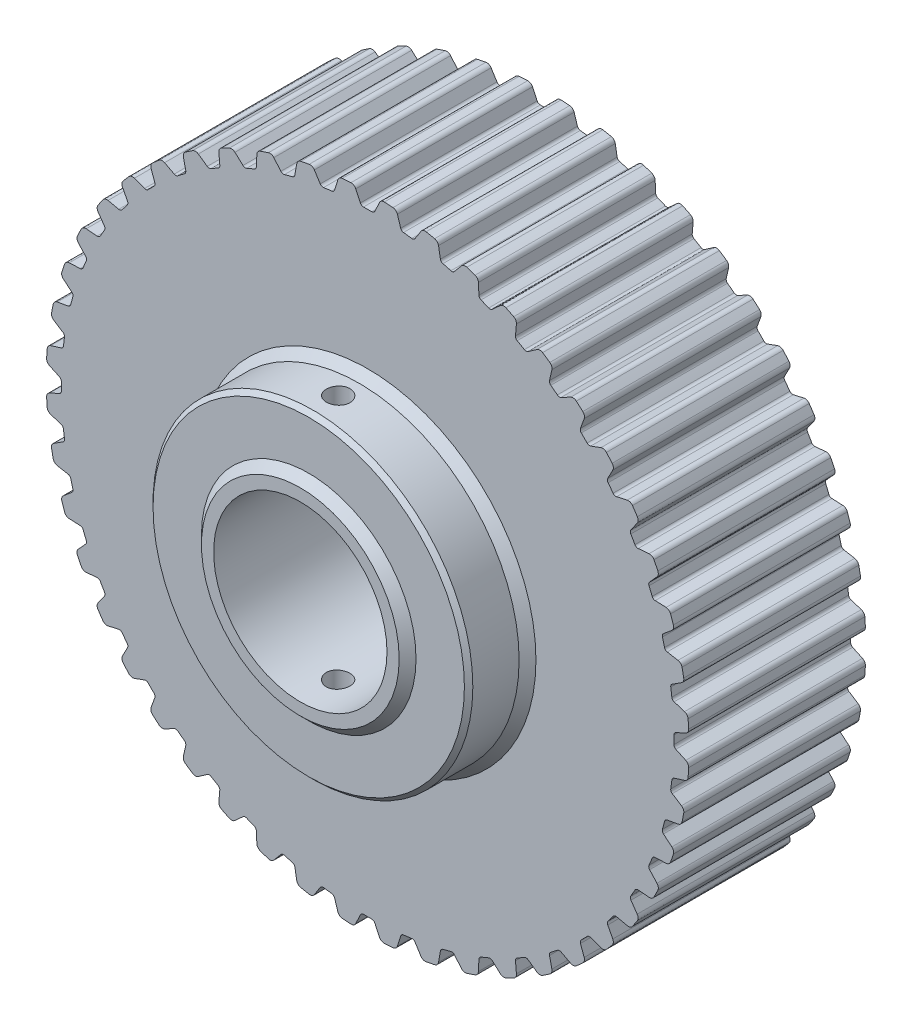
SolidWorks part; units mm, degrees
material "ABS"
ref_plane "Front Plane" through (0, 0, 0) normal (0, 0, 1) x (1, 0, 0)
ref_plane "Top Plane" through (0, 0, 0) normal (0, 1, 0) x (1, 0, 0)
ref_plane "Right Plane" through (0, 0, 0) normal (1, 0, 0) x (0, 0, -1)
sketch "Sketch1" plane through (0, 0, 0) normal (0, 0, 1) x (1, 0, 0)
  circle A0 centre (0, 0) radius 38.1972
  dimension "D1" = 76.3944
extrude "Boss-Extrude1" add sketch "Sketch1" along normal blind 21
sketch "Sketch2" plane through (0, 0, 21) normal (0, 0, 1) x (1, 0, 0)
  circle A0 centre (0, 0) radius 19
  dimension "D1" = 38
extrude "Boss-Extrude2" add sketch "Sketch2" along normal blind 7
sketch "Sketch3" plane through (0, 0, 28) normal (0, 0, 1) x (1, 0, 0)
  circle A0 centre (0, 0) radius 10.3
  dimension "D1" = 20.6
extrude "Cut-Extrude1" cut sketch "Sketch3" against normal through all
sketch "Sketch4" plane through (0, 0, 21) normal (0, 0, 1) x (1, 0, 0)
  line L1 (-1.593, 38.1972) -> (-0.75, 36.3895)
  line L2 (1.593, 38.1972) -> (0.75, 36.3895)
  line L3 (0, -44.7868) -> (0, 44.7868) construction
  line L4 (-1.593, 38.1972) -> (1.593, 38.1972)
  circle A0 centre (0, 0) radius 36.3972 construction
  arc A2 (-0.75, 36.3895) -> (0.75, 36.3895) centre (0, 0) cw
  circle A3 centre (0, 0) radius 38.1972 construction
  circle A4 centre (0, 0) radius 38.1972 construction
  point P11 (0, 36.3972)
  dimension "D1" = 1.8
  dimension "D2" = 25
  dimension "D4" = 1.5
  dimension "D3" = 25
extrude "Cut-Extrude2" cut sketch "Sketch4" against normal through all
fillet "Fillet1" radius 0.4 2 edges at (0.75, 36.3895, 10.5) (-0.75, 36.3895, 10.5)
fillet "Fillet2" radius 0.6 2 edges at (1.5778, 38.1646, 10.5) (-1.5778, 38.1646, 10.5)
ref_axis "Axis1" through (0, 0, 0) along (0, 0, 1)
pattern_circular "CirPattern1" count 48 over 360 about axis through (0, 0, 0) along (0, 0, 1) of "Cut-Extrude2", "Fillet1", "Fillet2"
sketch "Sketch5" plane through (0, 0, 21) normal (0, 0, 1) x (1, 0, 0)
  circle A0 centre (0, 0) radius 26 construction
  circle A1 centre (0, 26) radius 6
  dimension "D1" = 52
  dimension "D2" = 12
extrude "Cut-Extrude3" [suppressed] cut sketch "Sketch5" against normal through all
ref_axis "Axis2" through (0, 0, 0) along (0, 0, 1)
pattern_circular "CirPattern2" [suppressed] count 8 over 360 about axis through (0, 0, 0) along (0, 0, 1) of bodies 113
sketch "Sketch6" plane through (0, 0, 28) normal (0, 0, 1) x (1, 0, 0)
  circle A0 centre (0, 0) radius 10.3
  circle A1 centre (0, 0) radius 11.75
  circle A2 centre (0, 0) radius 10.3 construction
  dimension "D1" = 23.5
extrude "Boss-Extrude3" add sketch "Sketch6" along normal blind 1
chamfer "Chamfer1" distance 1 angle 45 1 edges at (11.75, 0, 28)
chamfer "Chamfer2" distance 1 angle 45 1 edges at (19, 0, 21)
sketch "Sketch9" plane through (0, 0, 0) normal (0, 1, 0) x (1, 0, 0)
  line L0 (0, -21) -> (0, -28) construction
  line L1 (-0.4918, -21) -> (0.4918, -21) construction
  line L2 (-12.75, -28) -> (12.75, -28) construction
  circle A0 centre (0, -24.5) radius 1.4
  point P9 (0, -24.5)
  dimension "D1" = 2.8
extrude "Cut-Extrude5" cut sketch "Sketch9" against normal mid plane 40
chamfer "Chamfer3" distance 0.5 angle 45 1 edges at (19, 0, 28)
